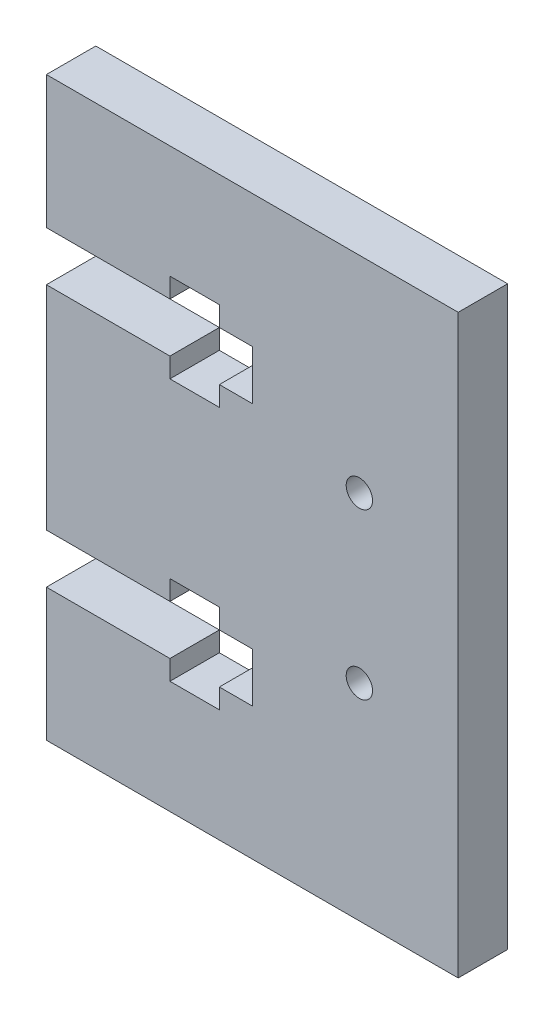
SolidWorks part; units mm, degrees
ref_plane "Front Plane" through (0, 0, 0) normal (0, 0, 1) x (1, 0, 0)
ref_plane "Top Plane" through (0, 0, 0) normal (0, 1, 0) x (1, 0, 0)
ref_plane "Right Plane" through (0, 0, 0) normal (1, 0, 0) x (0, 0, -1)
sketch "Sketch1" plane through (0, 0, 0) normal (0, 0, 1) x (1, 0, 0)
  line L0 (-97, 18.9) -> (-97, 21.3) construction
  line L1 (-68, -35) -> (-118, -35)
  line L2 (-68, -35) -> (-68, 35)
  line L3 (-68, 35) -> (-118, 35)
  line L4 (-118, -35) -> (-118, -18.9)
  line L5 (-68, -35) -> (-118, 35) construction
  line L6 (-68, 35) -> (-118, -35) construction
  line L7 (-93, 12.9) -> (-93, 18.9) construction
  line L8 (-97, 12.9) -> (-93, 12.9) construction
  line L9 (-97, 10.5) -> (-97, 12.9) construction
  line L10 (-103, 12.9) -> (-103, 10.5) construction
  line L11 (-103, 10.5) -> (-97, 10.5) construction
  line L12 (-118, 12.9) -> (-103, 12.9) construction
  line L13 (-103, 18.9) -> (-118, 18.9) construction
  line L14 (-103, 21.3) -> (-103, 18.9) construction
  line L15 (-97, 21.3) -> (-103, 21.3) construction
  line L16 (-93, 18.9) -> (-97, 18.9) construction
  line L17 (-97, 18.9) -> (-97, 21.3)
  line L18 (-93, 12.9) -> (-93, 18.9)
  line L19 (-97, 12.9) -> (-93, 12.9)
  line L20 (-97, 10.5) -> (-97, 12.9)
  line L21 (-103, 12.9) -> (-103, 10.5)
  line L22 (-103, 10.5) -> (-97, 10.5)
  line L23 (-118, 12.9) -> (-103, 12.9)
  line L24 (-103, 18.9) -> (-118, 18.9)
  line L25 (-103, 21.3) -> (-103, 18.9)
  line L26 (-97, 21.3) -> (-103, 21.3)
  line L27 (-93, 18.9) -> (-97, 18.9)
  line L38 (-97, -10.5) -> (-103, -10.5) construction
  line L39 (-97, -12.9) -> (-97, -10.5) construction
  line L40 (-93, -12.9) -> (-97, -12.9) construction
  line L41 (-103, -18.9) -> (-103, -21.3) construction
  line L42 (-93, -18.9) -> (-93, -12.9) construction
  line L43 (-97, -18.9) -> (-93, -18.9) construction
  line L44 (-97, -21.3) -> (-97, -18.9) construction
  line L45 (-103, -21.3) -> (-97, -21.3) construction
  line L46 (-118, -18.9) -> (-103, -18.9) construction
  line L47 (-103, -12.9) -> (-118, -12.9) construction
  line L48 (-103, -10.5) -> (-103, -12.9) construction
  line L49 (-103, -10.5) -> (-103, -12.9)
  line L50 (-97, -10.5) -> (-103, -10.5)
  line L51 (-97, -12.9) -> (-97, -10.5)
  line L52 (-93, -12.9) -> (-97, -12.9)
  line L53 (-103, -18.9) -> (-103, -21.3)
  line L54 (-93, -18.9) -> (-93, -12.9)
  line L55 (-97, -18.9) -> (-93, -18.9)
  line L56 (-97, -21.3) -> (-97, -18.9)
  line L57 (-103, -21.3) -> (-97, -21.3)
  line L58 (-118, -18.9) -> (-103, -18.9)
  line L59 (-103, -12.9) -> (-118, -12.9)
  line L60 (-118, -12.9) -> (-118, 12.9)
  line L61 (-118, 18.9) -> (-118, 35)
  circle A0 centre (-80, -10) radius 1.6 construction
  circle A1 centre (-80, 10) radius 1.6 construction
  circle A2 centre (-80, -10) radius 1.6
  circle A3 centre (-80, 10) radius 1.6
  point P0 (-93, 0)
  dimension "D1" = 50
extrude "Boss-Extrude1" add sketch "Sketch1" along normal blind 6
